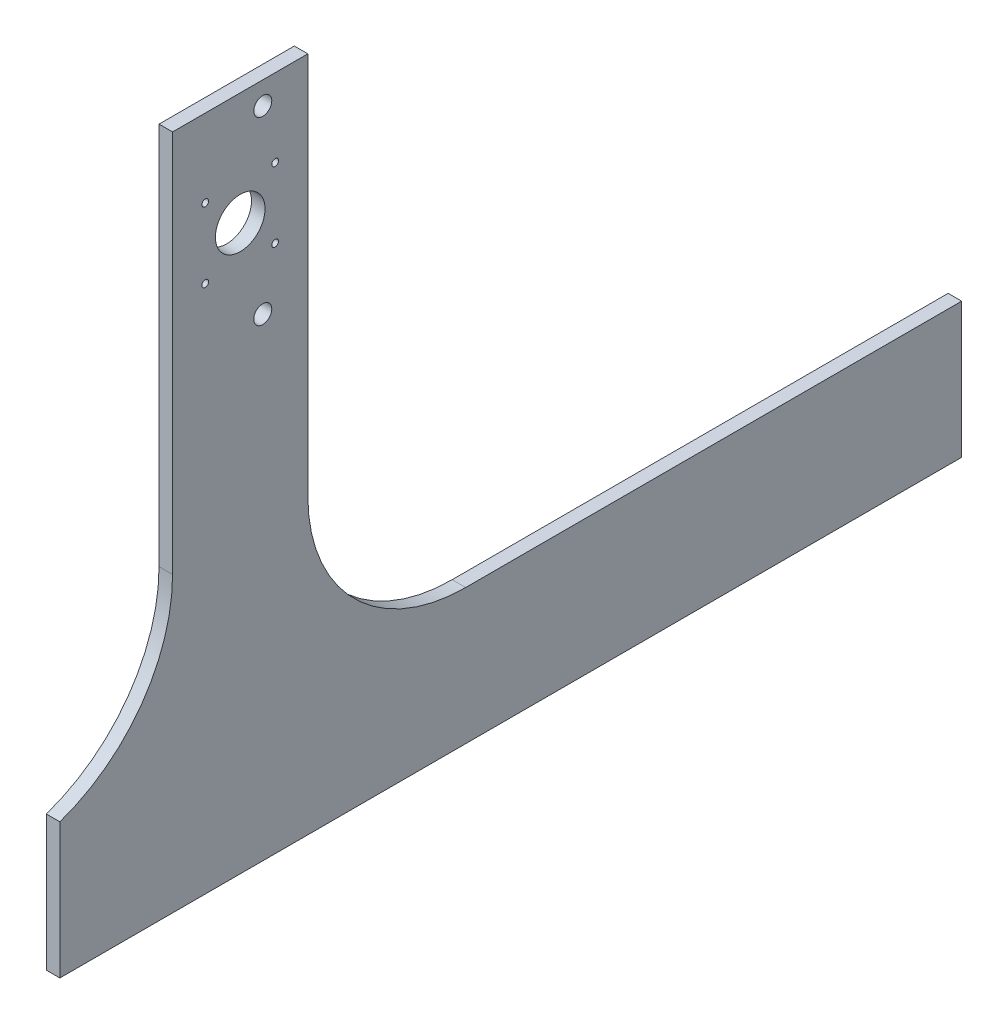
SolidWorks part; units mm, degrees
ref_plane "Front Plane" through (0, 0, 0) normal (0, 0, 1) x (1, 0, 0)
ref_plane "Top Plane" through (0, 0, 0) normal (0, 1, 0) x (1, 0, 0)
ref_plane "Right Plane" through (0, 0, 0) normal (1, 0, 0) x (0, 0, -1)
sketch "Sketch1" plane through (0, 0, 0) normal (1, 0, 0) x (0, 0, -1)
  line L0 (-1000, 0) -> (49000, 0) construction
  line L1 (-80, -300) -> (320, -300)
  line L4 (320, -300) -> (320, -240)
  line L6 (-80, -300) -> (-80, -240)
  line L7 (0, -1000) -> (0, 49000) construction
  line L10 (-30, 0) -> (-30, -170)
  line L11 (-1080, -240) -> (48920, -240) construction
  line L12 (-112.889, -170) -> (172.771, -170) construction
  line L20 (0, -750) -> (0, 49250) construction
  line L31 (30, 0) -> (30, -170)
  line L33 (100, -240) -> (320, -240)
  line L34 (-27.1942, -50) -> (27.1942, -50) construction
  line L37 (-30, 0) -> (30, 0)
  line L38 (10, -1000) -> (10, 49000) construction
  circle A2 centre (10, -90) radius 4
  circle A3 centre (10, -10) radius 4
  circle A4 centre (15.5, -34.5) radius 1.5
  arc A5 (100, -240) -> (30, -170) centre (100, -170) cw
  circle A6 centre (-15.5, -34.5) radius 1.5
  circle A7 centre (15.5, -65.5) radius 1.5
  circle A8 centre (-15.5, -65.5) radius 1.5
  circle A9 centre (0, -50) radius 11
  arc A12 (-80, -240) -> (-30, -170) centre (-104, -170) ccw
  point P0 (0, 0)
  point P51 (0, -50)
  point P62 (0, 0)
  dimension "D7" = 8
  dimension "D14" = 60
  dimension "D16" = 50
  dimension "D18" = 3
  dimension "D10" = 70
  dimension "D6" = 22
  dimension "D3" = 400
  dimension "D4" = 60
  dimension "D5" = 170
  dimension "D8" = 300
  dimension "D9" = 60
  dimension "D11" = 50
  dimension "D12" = 130
  dimension "D13" = 70
  dimension "D15" = 10
  dimension "D17" = 40
  dimension "D19" = 15.5
  dimension "D20" = 15.5
  dimension "D21" = 100
  dimension "D22" = 10
extrude "Boss-Extrude1" add sketch "Sketch1" along normal blind 6
